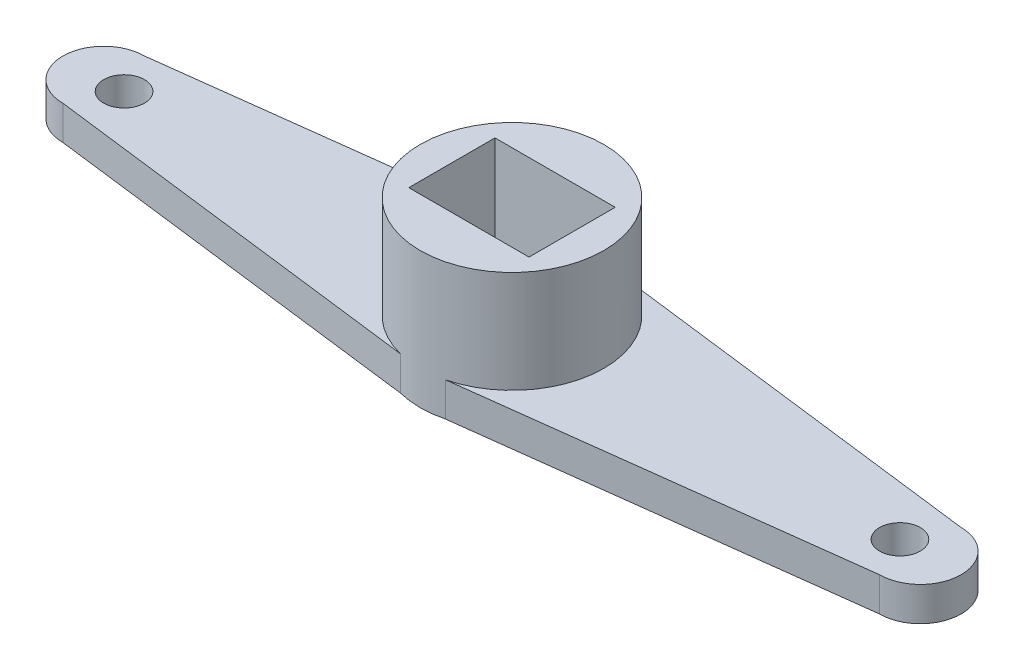
SolidWorks part; units mm, degrees
ref_plane "Front Plane" through (0, 0, 0) normal (0, 0, 1) x (1, 0, 0)
ref_plane "Top Plane" through (0, 0, 0) normal (0, 1, 0) x (1, 0, 0)
ref_plane "Right Plane" through (0, 0, 0) normal (1, 0, 0) x (0, 0, -1)
sketch "Sketch1" plane through (0, 0, 0) normal (0, 1, 0) x (1, 0, 0)
  line L1 (-2.65, -1.9) -> (2.65, -1.9)
  line L2 (-2.65, -1.9) -> (-2.65, 1.9)
  line L3 (-2.65, 1.9) -> (2.65, 1.9)
  line L4 (2.65, -1.9) -> (2.65, 1.9)
  line L5 (-2.65, -1.9) -> (2.65, 1.9) construction
  line L6 (-2.65, 1.9) -> (2.65, -1.9) construction
  circle A0 centre (0, 0) radius 4.05
  dimension "D1" = 5.3
  dimension "D3" = 8.1
  dimension "D2" = 3.8
sketch "Sketch2" plane through (0, 0, 0) normal (0, 1, 0) x (1, 0, 0)
  line L0 (0, 0) -> (18, 0) construction
  line L3 (0, 0) -> (-18, 0) construction
  line L6 (0, 0) -> (0, 4.05) construction
  line L7 (0, 0) -> (0, -4.05) construction
  line L8 (-18, 1.8) -> (0, 4.05)
  line L9 (0, 4.05) -> (18, 1.8)
  line L10 (18, -1.8) -> (0, -4.05)
  line L11 (0, -4.05) -> (-18, -1.8)
  arc A3 (-18, 1.8) -> (-18, -1.8) centre (-18, 0) ccw
  arc A4 (18, 1.8) -> (18, -1.8) centre (18, 0) cw
  point P7 (-19.8, 0)
  dimension "D2" = 18
  dimension "D3" = 1.8
  dimension "D1" = 18
extrude "Boss-Extrude1" add sketch "Sketch1" along normal blind 6
extrude "Boss-Extrude2" add sketch "Sketch2" along normal blind 1.5
sketch "Sketch3" plane through (0, 0, 0) normal (0, 1, 0) x (1, 0, 0)
  line L0 (-23.85, 0) -> (-2.65, 0) construction
  line L1 (-2.65, -1.9) -> (2.65, -1.9)
  line L2 (-2.65, -1.9) -> (-2.65, 1.9)
  line L3 (-2.65, 1.9) -> (2.65, 1.9)
  line L4 (2.65, -1.9) -> (2.65, 1.9)
  line L5 (-2.65, -1.9) -> (2.65, 1.9) construction
  line L6 (-2.65, 1.9) -> (2.65, -1.9) construction
  line L7 (2.65, 0) -> (23.85, 0) construction
  arc A2 (-22.05, 1.8) -> (-22.05, -1.8) centre (-22.05, 0) ccw construction
  arc A3 (22.05, -1.8) -> (22.05, 1.8) centre (22.05, 0) ccw construction
  circle A4 centre (-17.1, 0) radius 0.9
  circle A5 centre (17.1, 0) radius 0.9
  point P0 (0, 0)
  dimension "D1" = 1.8
extrude "Cut-Extrude1" cut sketch "Sketch3" along normal blind 1.5
